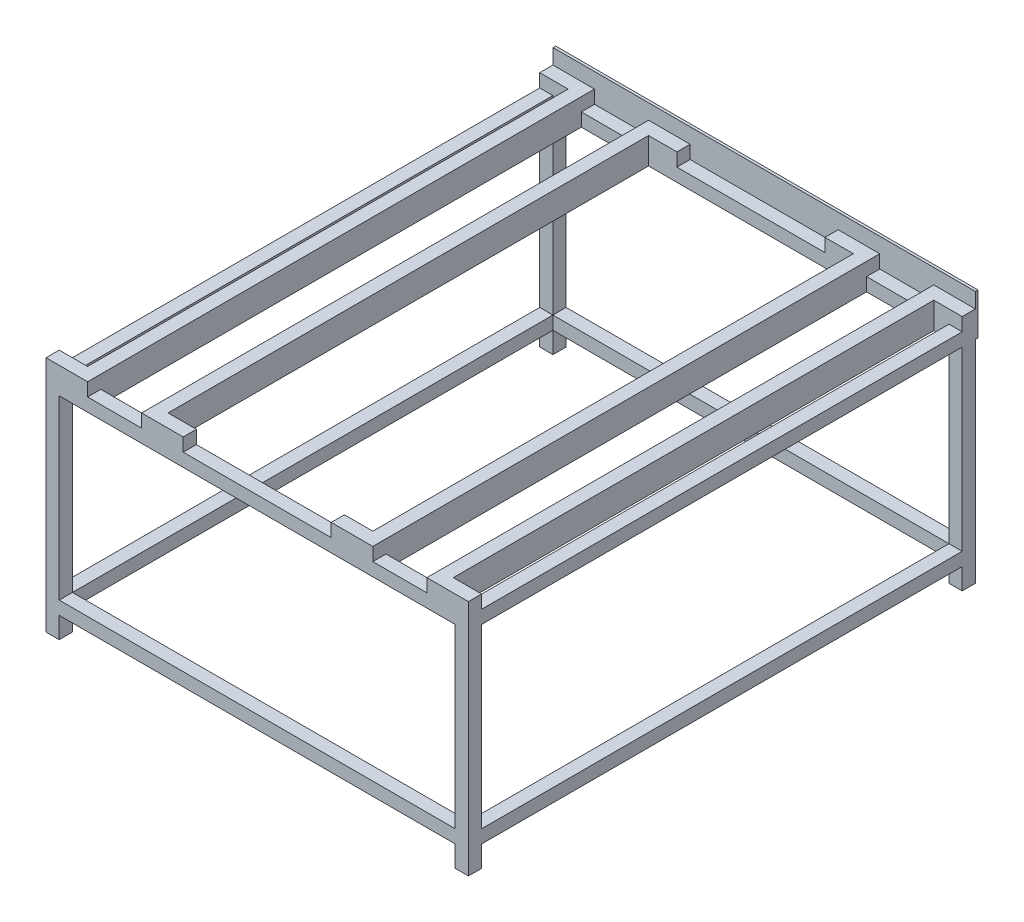
SolidWorks part; units mm, degrees
ref_plane "Front Plane" through (0, 0, 0) normal (0, 0, 1) x (1, 0, 0)
ref_plane "Top Plane" through (0, 0, 0) normal (0, 1, 0) x (1, 0, 0)
ref_plane "Right Plane" through (0, 0, 0) normal (1, 0, 0) x (0, 0, -1)
sketch "Sketch1" plane through (0, 0, 0) normal (0, 1, 0) x (1, 0, 0)
  line L1 (0, 0) -> (1016, 0)
  line L2 (0, 0) -> (0, 1219.2)
  line L3 (0, 1219.2) -> (1016, 1219.2)
  line L4 (1016, 0) -> (1016, 1219.2)
  dimension "D1" = 1016
  dimension "D2" = 1219.2
sketch "Sketch2" plane through (0, 0, 0) normal (0, 1, 0) x (1, 0, 0)
  line L1 (0, 1219.2) -> (31.75, 1219.2)
  line L2 (0, 1219.2) -> (0, 1187.45)
  line L3 (0, 1187.45) -> (31.75, 1187.45)
  line L4 (31.75, 1219.2) -> (31.75, 1187.45)
  line L5 (0, 0) -> (31.75, 0)
  line L6 (0, 0) -> (0, 31.75)
  line L7 (0, 31.75) -> (31.75, 31.75)
  line L8 (31.75, 0) -> (31.75, 31.75)
  line L9 (1016, 0) -> (984.25, 0)
  line L10 (1016, 0) -> (1016, 31.75)
  line L11 (1016, 31.75) -> (984.25, 31.75)
  line L12 (984.25, 0) -> (984.25, 31.75)
  line L13 (1016, 1219.2) -> (984.25, 1219.2)
  line L14 (1016, 1219.2) -> (1016, 1187.45)
  line L15 (1016, 1187.45) -> (984.25, 1187.45)
  line L16 (984.25, 1219.2) -> (984.25, 1187.45)
  dimension "D1" = 31.75
  dimension "D2" = 31.75
  dimension "D3" = 31.75
  dimension "D4" = 31.75
  dimension "D5" = 31.75
  dimension "D6" = 31.75
  dimension "D7" = 31.75
  dimension "D8" = 31.75
extrude "Boss-Extrude1" add sketch "Sketch2" along normal blind 508
sketch "Sketch3" plane through (0, 508, 0) normal (0, 1, 0) x (1, 0, 0)
  line L17 (0, 0) -> (1016, 0)
  line L18 (0, 0) -> (0, 1219.2)
  line L19 (0, 1219.2) -> (1016, 1219.2)
  line L20 (1016, 0) -> (1016, 1219.2)
  line L21 (31.75, 31.75) -> (984.25, 31.75)
  line L22 (31.75, 31.75) -> (31.75, 1187.45)
  line L23 (31.75, 1187.45) -> (984.25, 1187.45)
  line L24 (984.25, 31.75) -> (984.25, 1187.45)
extrude "Boss-Extrude2" add sketch "Sketch3" along normal blind 31.75
extrude "Boss-Extrude3" add sketch "Sketch3<2>" along normal blind 31.75 from offset 457.2 offset against normal yes
sketch "Sketch3<2>" plane through (0, 508, 0) normal (0, 1, 0) x (1, 0, 0) same geometry as "Sketch3"
sketch "Sketch4" plane through (0, 539.75, 0) normal (0, 1, 0) x (1, 0, 0)
  line L0 (984.25, 1187.45) -> (31.75, 1187.45) construction
  line L1 (0, 1219.2) -> (100, 1219.2)
  line L2 (0, 1219.2) -> (0, 1187.45)
  line L3 (0, 1187.45) -> (100, 1187.45)
  line L4 (100, 1219.2) -> (100, 1187.45)
  line L5 (0, 1219.2) -> (1016, 1219.2) construction
  line L6 (230, 1219.2) -> (330, 1219.2)
  line L7 (230, 1219.2) -> (230, 1187.45)
  line L8 (230, 1187.45) -> (330, 1187.45)
  line L9 (330, 1219.2) -> (330, 1187.45)
  line L10 (0, 609.6) -> (1016, 609.6) construction
  line L11 (1016, 1219.2) -> (916, 1219.2)
  line L12 (1016, 1219.2) -> (1016, 1187.45)
  line L13 (1016, 1187.45) -> (916, 1187.45)
  line L14 (916, 1219.2) -> (916, 1187.45)
  line L15 (786, 1219.2) -> (686, 1219.2)
  line L16 (786, 1219.2) -> (786, 1187.45)
  line L17 (786, 1187.45) -> (686, 1187.45)
  line L18 (686, 1219.2) -> (686, 1187.45)
  line L19 (0, 0) -> (0, 1219.2) construction
  line L20 (1016, 0) -> (1016, 1219.2) construction
  line L21 (686, 0) -> (686, 31.75)
  line L22 (786, 31.75) -> (686, 31.75)
  line L23 (786, 0) -> (786, 31.75)
  line L24 (786, 0) -> (686, 0)
  line L25 (916, 0) -> (916, 31.75)
  line L26 (1016, 31.75) -> (916, 31.75)
  line L27 (1016, 0) -> (1016, 31.75)
  line L28 (1016, 0) -> (916, 0)
  line L29 (330, 0) -> (330, 31.75)
  line L30 (230, 31.75) -> (330, 31.75)
  line L31 (230, 0) -> (230, 31.75)
  line L32 (230, 0) -> (330, 0)
  line L33 (100, 0) -> (100, 31.75)
  line L34 (0, 31.75) -> (100, 31.75)
  line L35 (0, 0) -> (0, 31.75)
  line L36 (0, 0) -> (100, 0)
  dimension "D1" = 100
  dimension "D2" = 130
  dimension "D3" = 130
extrude "Boss-Extrude4" add sketch "Sketch4" along normal blind 31.75
sketch "Sketch5" plane through (0, 0, -1187.45) normal (0, 0, 1) x (1, 0, 0)
  line L0 (31.75, 508) -> (984.25, 508) construction
  line L1 (100, 571.5) -> (68.25, 571.5)
  line L2 (100, 571.5) -> (100, 508)
  line L3 (100, 508) -> (68.25, 508)
  line L4 (68.25, 571.5) -> (68.25, 508)
  line L6 (230, 571.5) -> (261.75, 571.5)
  line L7 (230, 571.5) -> (230, 508)
  line L8 (230, 508) -> (261.75, 508)
  line L9 (261.75, 571.5) -> (261.75, 508)
  line L10 (786, 571.5) -> (754.25, 571.5)
  line L11 (786, 571.5) -> (786, 508)
  line L12 (786, 508) -> (754.25, 508)
  line L13 (754.25, 571.5) -> (754.25, 508)
  line L14 (916, 571.5) -> (947.75, 571.5)
  line L15 (916, 571.5) -> (916, 508)
  line L16 (916, 508) -> (947.75, 508)
  line L17 (947.75, 571.5) -> (947.75, 508)
  dimension "D1" = 31.75
extrude "Boss-Extrude5" add sketch "Sketch5" along normal up to surface (1155.7 mm away) up to face at (508, 549.275, -31.75)
sketch "Sketch6" plane through (0, 0, -1219.2) normal (0, 0, -1) x (-1, 0, 0)
  line L1 (-1016, 508) -> (0, 508)
  line L2 (-1016, 508) -> (-1016, 608)
  line L3 (-1016, 608) -> (0, 608)
  line L4 (0, 508) -> (0, 608)
  dimension "D1" = 100
extrude "Boss-Extrude6" add sketch "Sketch6" along normal blind 6.35
